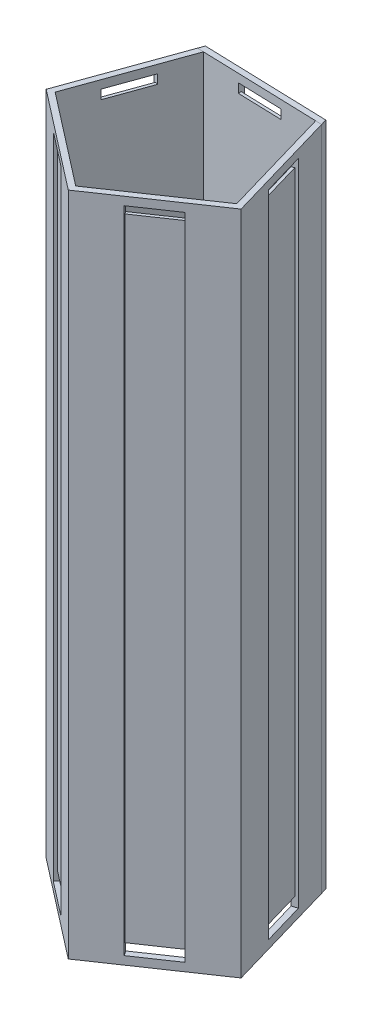
SolidWorks part; units mm, degrees
ref_plane "Front Plane" through (0, 0, 0) normal (0, 0, 1) x (1, 0, 0)
ref_plane "Top Plane" through (0, 0, 0) normal (0, 1, 0) x (1, 0, 0)
ref_plane "Right Plane" through (0, 0, 0) normal (1, 0, 0) x (0, 0, -1)
sketch "Sketch2" plane through (0, 0, 0) normal (0, 1, 0) x (1, 0, 0)
  line L0 (17.7243, 22.8571) -> (-16.2613, 23.92)
  line L1 (25.3546, -9.1239) -> (16.5123, 21.2942)
  line L2 (16.5123, 21.2942) -> (-15.1494, 22.2845)
  line L3 (-15.1494, 22.2845) -> (-25.8752, -7.5217)
  line L4 (-25.8752, -7.5217) -> (-0.8423, -26.9331)
  line L5 (-0.8423, -26.9331) -> (25.3546, -9.1239)
  line L6 (-16.2613, 23.92) -> (-27.7743, -8.0737)
  line L7 (-27.7743, -8.0737) -> (-0.9041, -28.9099)
  line L8 (-0.9041, -28.9099) -> (27.2155, -9.7935)
  line L9 (27.2155, -9.7935) -> (17.7243, 22.8571)
  circle A0 centre (0, 0) radius 21.8 construction
  dimension "D1" = 43.6
  dimension "D2" = 1.6
extrude "Boss-Extrude2" add sketch "Sketch2" along normal blind 182
sketch "Sketch3" plane through (0.7315, 0, -23.3886) normal (0.0313, 0, -0.9995) x (-0.9995, 0, -0.0313)
  line L1 (-6, 178.5) -> (6, 178.5)
  line L2 (-6, 178.5) -> (-6, 3.5)
  line L3 (-6, 3.5) -> (6, 3.5)
  line L4 (6, 178.5) -> (6, 3.5)
  line L5 (-6, 178.5) -> (6, 3.5) construction
  line L6 (-6, 3.5) -> (6, 178.5) construction
  line L7 (-17.0011, 182) -> (17.0011, 0) construction
  line L8 (-17.0011, 0) -> (17.0011, 182) construction
  point P0 (0, 91)
  point P8 (0, 91)
  dimension "D1" = 12
  dimension "D2" = 175
extrude "Cut-Extrude1" cut sketch "Sketch3" against normal blind 0.8
sketch "Sketch4" plane through (0.7315, 0, -23.3886) normal (0.0313, 0, -0.9995) x (-0.9995, 0, -0.0313)
  line L0 (-6, 3.5) -> (6, 3.5) construction
  line L1 (-6, 178.5) -> (-6, 3.5) construction
  line L2 (6, 2.25) -> (-6, 2.25)
  line L3 (6, 2.25) -> (6, 4.75)
  line L4 (6, 4.75) -> (-6, 4.75)
  line L5 (-6, 2.25) -> (-6, 4.75)
  line L6 (6, 2.25) -> (-6, 4.75) construction
  line L7 (6, 4.75) -> (-6, 2.25) construction
  line L13 (-6, 91) -> (6, 91) construction
  line L14 (6, 3.5) -> (6, 178.5) construction
  line L15 (6, 177.25) -> (-6, 179.75) construction
  line L16 (6, 179.75) -> (-6, 177.25) construction
  line L17 (-6, 179.75) -> (-6, 177.25)
  line L18 (6, 177.25) -> (-6, 177.25)
  line L19 (6, 179.75) -> (6, 177.25)
  line L20 (6, 179.75) -> (-6, 179.75)
  point P2 (0, 3.5)
  point P17 (0, 178.5)
  dimension "D1" = 2.5
extrude "Cut-Extrude2" cut sketch "Sketch4" against normal blind 5
ref_plane "Plane1" through (0, 182, 0) normal (0, 1, 0) x (1, 0, 0)
ref_axis "Axis1" through (0, 0, 0) along (0, 1, 0)
pattern_circular "CirPattern1" count 5 over 360 about axis through (0, 0, 0) along (0, 1, 0) of "Cut-Extrude1", "Cut-Extrude2"
ref_plane "Plane2" through (0.6815, 0, -21.7893) normal (-0.0313, 0, 0.9995) x (0.9995, 0, 0.0313)
split "Split1" trim tools "Plane2" bodies to split 104 resulting bodies 111 112
